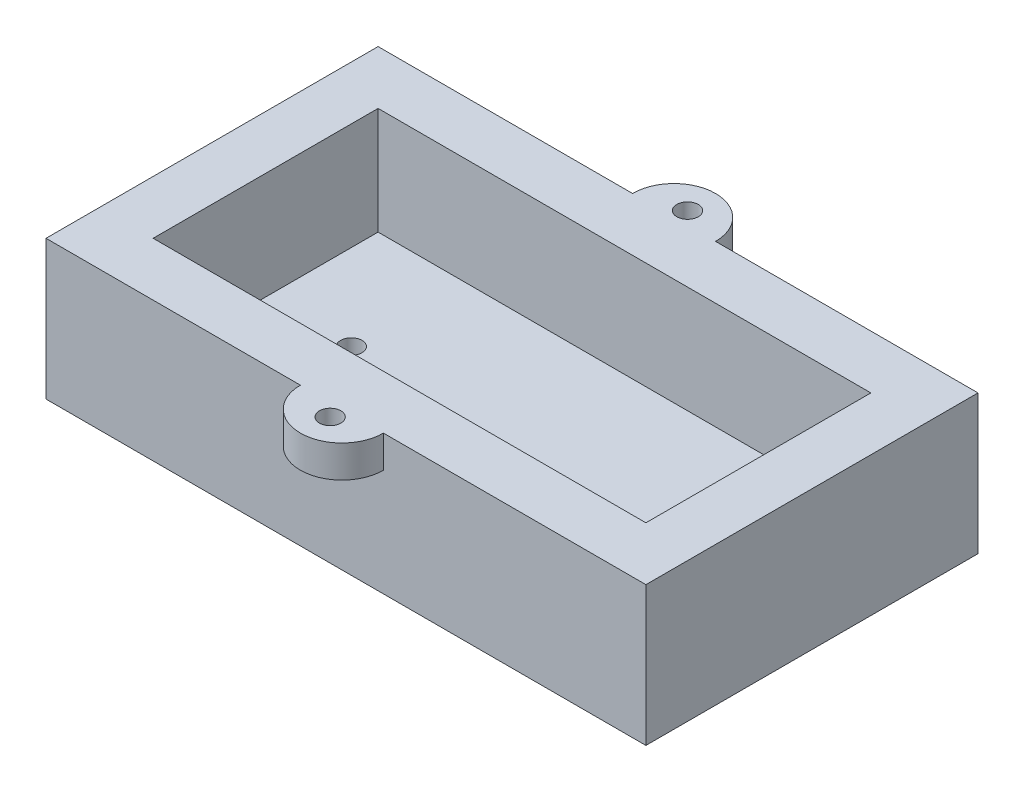
SolidWorks part; units mm, degrees
ref_plane "Front Plane" through (0, 0, 0) normal (0, 0, 1) x (1, 0, 0)
ref_plane "Top Plane" through (0, 0, 0) normal (0, 1, 0) x (1, 0, 0)
ref_plane "Right Plane" through (0, 0, 0) normal (1, 0, 0) x (0, 0, -1)
sketch "Sketch1" plane through (0, 0, 0) normal (0, 1, 0) x (1, 0, 0)
  line L1 (-17.8361, 15.1639) -> (28.1639, 15.1639)
  line L2 (-17.8361, 15.1639) -> (-17.8361, -5.8361)
  line L3 (-17.8361, -5.8361) -> (28.1639, -5.8361)
  line L4 (28.1639, 15.1639) -> (28.1639, -5.8361)
  line L5 (-22.8361, 20.1639) -> (33.1639, 20.1639)
  line L6 (-22.8361, 20.1639) -> (-22.8361, -10.8361)
  line L7 (-22.8361, -10.8361) -> (33.1639, -10.8361)
  line L8 (33.1639, 20.1639) -> (33.1639, -10.8361)
  dimension "D1" = 46
  dimension "D2" = 21
  dimension "D3" = 5
  dimension "D4" = 5
  dimension "D5" = 5
  dimension "D6" = 5
extrude "Boss-Extrude4" add sketch "Sketch1" along normal blind 3 contours L2 L1 L4 L3
extrude "Boss-Extrude5" add sketch "Sketch1<5>" along normal blind 13
sketch "Sketch1<5>" plane through (0, 0, 0) normal (0, 1, 0) x (1, 0, 0) same geometry as "Sketch1"
sketch "Sketch4" plane through (0, 13, 0) normal (0, 1, 0) x (1, 0, 0)
  line L0 (5.1639, 20.1639) -> (5.1639, -10.8361) construction
  line L1 (33.1639, 20.1639) -> (-22.8361, 20.1639) construction
  line L2 (-22.8361, -10.8361) -> (33.1639, -10.8361) construction
  line L3 (0.9136, 20.1639) -> (8.6642, 20.1639)
  line L4 (-22.8361, 4.6639) -> (33.1639, 4.6639) construction
  line L5 (-22.8361, 20.1639) -> (-22.8361, -10.8361) construction
  line L6 (33.1639, -10.8361) -> (33.1639, 20.1639) construction
  line L7 (0.9136, -10.8361) -> (8.6642, -10.8361)
  arc A0 (0.9136, 20.1639) -> (8.6642, 20.1639) centre (4.7889, 20.1639) cw
  arc A1 (0.9136, -10.8361) -> (8.6642, -10.8361) centre (4.7889, -10.8361) ccw
extrude "Boss-Extrude6" add sketch "Sketch4" against normal blind 3
sketch "Sketch5" plane through (0, 13, 0) normal (0, 1, 0) x (1, 0, 0)
  line L0 (-22.8361, 4.6639) -> (33.1639, 4.6639) construction
  line L1 (-22.8361, 20.1639) -> (-22.8361, -10.8361) construction
  line L2 (33.1639, -10.8361) -> (33.1639, 20.1639) construction
  circle A0 centre (4.8691, 21.3455) radius 1
  circle A1 centre (4.8691, -12.0176) radius 1
  dimension "D1" = 2
extrude "Cut-Extrude1" cut sketch "Sketch5" against normal blind 1.5
sketch "Sketch6" plane through (0, 3, 0) normal (0, 1, 0) x (1, 0, 0)
  line L0 (-17.8361, 4.6639) -> (28.1639, 4.6639) construction
  line L1 (-17.8361, 15.1639) -> (-17.8361, -5.8361) construction
  line L2 (28.1639, -5.8361) -> (28.1639, 15.1639) construction
  line L3 (5.1639, 15.1639) -> (5.1639, -5.8361) construction
  line L4 (28.1639, 15.1639) -> (-17.8361, 15.1639) construction
  line L5 (-17.8361, -5.8361) -> (28.1639, -5.8361) construction
  circle A0 centre (-9.8361, 4.6639) radius 1
  circle A1 centre (20.1639, 4.6639) radius 1
  dimension "D1" = 8
extrude "Cut-Extrude2" cut sketch "Sketch6" against normal blind 5
sketch "Sketch7" plane through (0, 13, 0) normal (0, 1, 0) x (1, 0, 0)
  line L0 (0.9136, -10.8361) -> (8.6642, -10.8361) construction
